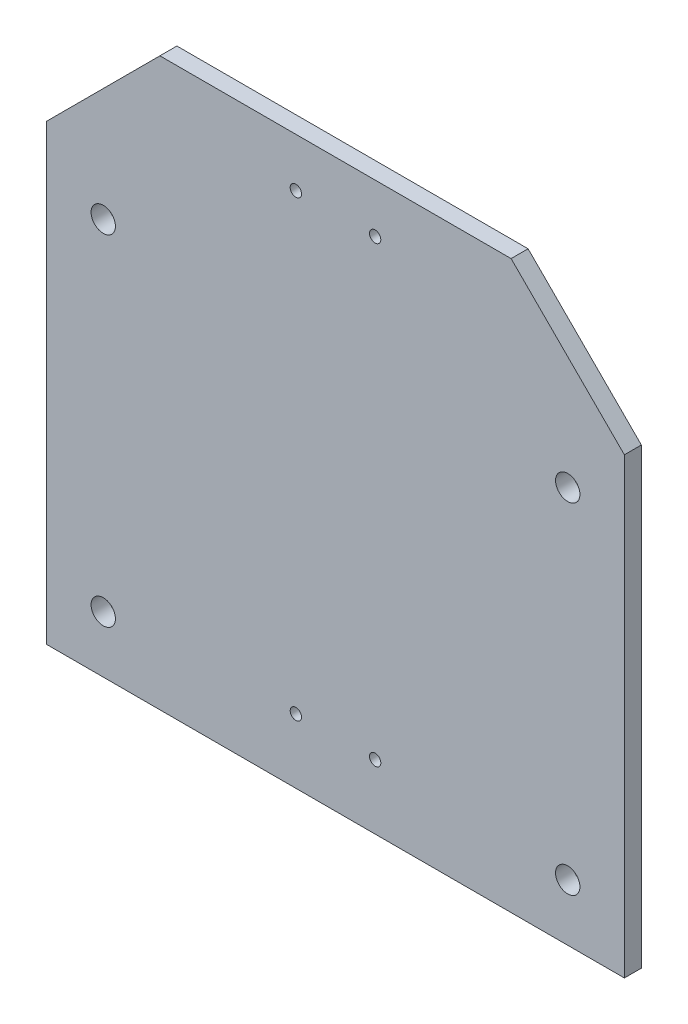
SolidWorks part; units mm, degrees
ref_plane "前视基准面" through (0, 0, 0) normal (0, 0, 1) x (1, 0, 0)
ref_plane "上视基准面" through (0, 0, 0) normal (0, 1, 0) x (1, 0, 0)
ref_plane "右视基准面" through (0, 0, 0) normal (1, 0, 0) x (0, 0, -1)
sketch "草图1" plane through (0, 0, 0) normal (0, 0, 1) x (1, 0, 0)
  line L0 (-51.0025, -60.1275) -> (51.0025, -60.1275)
  line L1 (-51.0025, -166.886) -> (-51.0025, 19.8725) construction
  line L2 (51.0025, 19.8725) -> (51.0025, -166.8866) construction
  line L3 (51.0025, -60.1275) -> (51.0025, 19.8725)
  line L4 (51.0025, 19.8725) -> (31.0025, 39.8725) construction
  line L5 (51.0025, 19.8725) -> (31.0025, 39.8725)
  line L6 (31.0025, 39.8725) -> (-31.0025, 39.8725)
  line L7 (-31.0025, 39.8725) -> (-51.0025, 19.8725)
  line L8 (-51.0025, 19.8725) -> (-51.0025, -60.1275)
  dimension "D1" = 100
extrude "凸台-拉伸1" add sketch "草图1" against normal blind 3
sketch "草图2" plane through (0, 0, 0) normal (0, 0, 1) x (1, 0, 0)
  circle A0 centre (-41.0025, 9.8725) radius 2.15
  circle A1 centre (-41.0025, -50.1275) radius 2.15
  circle A2 centre (41.0025, 9.8725) radius 2.15
  circle A3 centre (41.0025, -50.1275) radius 2.15
extrude "切除-拉伸1" cut sketch "草图2" against normal blind 3
sketch "草图3" plane through (0, 0, -3) normal (0, 0, -1) x (-1, 0, 0)
  circle A0 centre (-7.0002, 31.25) radius 1
  circle A1 centre (6.9998, 31.25) radius 1
  circle A2 centre (-7.0002, -48.75) radius 1
  circle A3 centre (6.9998, -48.75) radius 1
extrude "切除-拉伸2" cut sketch "草图3" against normal blind 70
